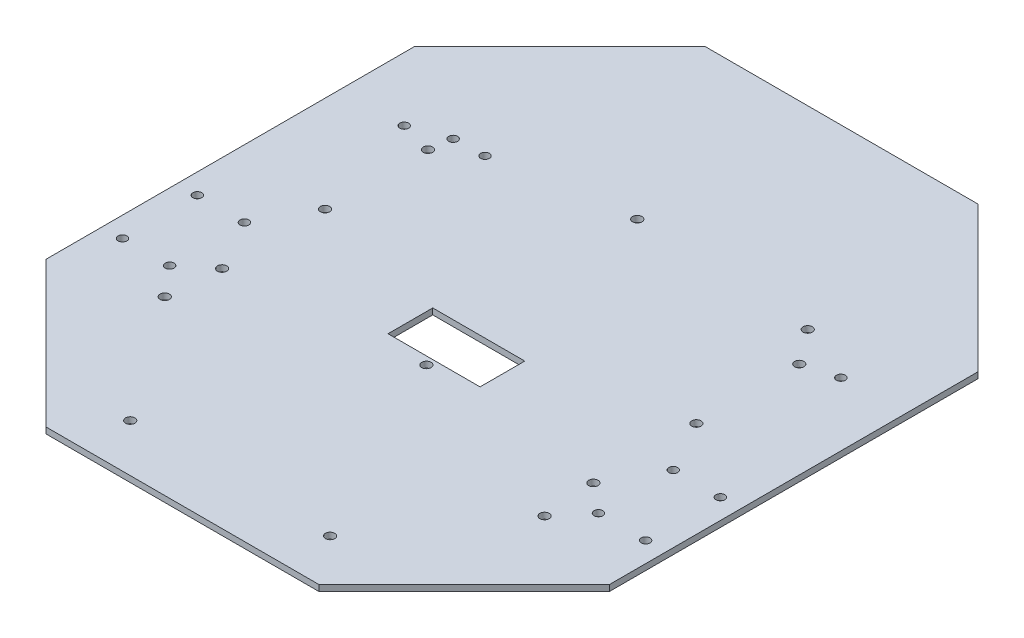
SolidWorks part; units mm, degrees
ref_plane "Front Plane" through (0, 0, 0) normal (0, 0, 1) x (1, 0, 0)
ref_plane "Top Plane" through (0, 0, 0) normal (0, 1, 0) x (1, 0, 0)
ref_plane "Right Plane" through (0, 0, 0) normal (1, 0, 0) x (0, 0, -1)
sketch "Sketch14" plane through (0, 0, 0) normal (0, 1, 0) x (1, 0, 0)
  line L1 (224, 92.7838) -> (92.7838, 224)
  line L2 (92.7838, 224) -> (-92.7838, 224)
  line L3 (-92.7838, 224) -> (-224, 92.7838)
  line L4 (-224, 92.7838) -> (-224, -92.7838)
  line L5 (-224, -92.7838) -> (-92.7838, -224)
  line L6 (-92.7838, -224) -> (92.7838, -224)
  line L7 (92.7838, -224) -> (224, -92.7838)
  line L8 (224, -92.7838) -> (224, 92.7838)
  circle A0 centre (0, 0) radius 224 construction
extrude "Boss-Extrude2" add sketch "Sketch14" along normal blind 4.12
sketch "Sketch16" plane through (0, 0, 0) normal (0, -1, 0) x (1, 0, 0)
  line L0 (-191.5, -224) -> (-191.5, 224)
  line L1 (-191.5, -224) -> (191.5, -224)
  line L2 (-191.5, 224) -> (191.5, 224)
  line L3 (191.5, -224) -> (191.5, 224)
  line L4 (-191.5, -224) -> (191.5, 224) construction
  line L5 (-191.5, 224) -> (191.5, -224) construction
  point P1 (0, 0)
  dimension "D1" = 383
ref_point "Point9"
ref_point "Point10"
sketch "Sketch17" plane through (0, 0, 0) normal (0, -1, 0) x (1, 0, 0)
  line L0 (191.5, 125.2838) -> (191.5, -125.742)
  line L1 (191.5, -125.742) -> (224, -92.7838)
  line L2 (224, -92.7838) -> (224, 92.7838)
  line L3 (224, 92.7838) -> (191.5, 125.2838)
extrude "Cut-Extrude2" cut sketch "Sketch17" against normal blind 4.12
ref_point "Point11"
ref_point "Point12"
sketch "Sketch18" plane through (0, 0, 0) normal (0, -1, 0) x (1, 0, 0)
  line L0 (-191.5, 125.2838) -> (-224, 92.7838)
  line L1 (-224, 92.7838) -> (-224, -92.7838)
  line L2 (-224, -92.7838) -> (-191.5, -125.2838)
  line L3 (-191.5, -125.2838) -> (-191.5, 125.2838)
extrude "Cut-Extrude3" cut sketch "Sketch18" against normal blind 4.12
hole_wizard "1/4 (0.25) Diameter Hole1" positions "Sketch19" profile "Sketch21" hole size "1/4" standard "ANSI Inch" end condition up to next
sketch "Sketch19" plane through (0, 4.12, 0) normal (0, 1, 0) x (1, 0, 0)
  point P2 (67.9635, -191.609)
  point P5 (-67.9265, -191.609)
  point P8 (-129.0643, -106.9889)
  point P11 (-126.1941, -70.8955)
  point P14 (-126.1941, -0.9185)
  point P17 (-126.1941, 69.0585)
  point P20 (-14.1039, 99.2591)
  point P23 (108.7305, 92.2995)
  point P26 (126.2311, 69.0585)
  point P29 (126.2311, -0.9185)
  point P32 (129.1013, -106.9889)
  point P35 (126.2311, -70.8955)
  point P38 (0.0185, -58.1955)
sketch "Sketch21" plane through (67.9635, 4.12, 191.609) normal (1, 0, 0) x (0, 0, 1)
  line L0 (0, 0) -> (0, 4.12)
  line L1 (0, 4.12) -> (3.175, 4.12)
  line L2 (3.175, 4.12) -> (3.175, 0)
  line L5 (3.175, 0) -> (0, 0)
  line L11 (0, -6.35) -> (0, 107.95) construction
  dimension "Thru Hole Dia." = 6.35
  dimension "Thru Hole Depth" = 4.12
sketch "Sketch22" plane through (0, 4.12, 0) normal (0, 1, 0) x (1, 0, 0)
  line L1 (31.1658, -52.8764) -> (-31.3997, -52.8764)
  line L2 (31.1658, -52.8764) -> (31.1658, -22.4822)
  line L3 (31.1658, -22.4822) -> (-31.3997, -22.4822)
  line L4 (-31.3997, -52.8764) -> (-31.3997, -22.4822)
extrude "Cut-Extrude4" cut sketch "Sketch22" against normal up to next
sketch "Sketch23" plane through (0, 0, 224) normal (0, 0, 1) x (1, 0, 0)
  line L0 (0, 4.12) -> (0, 0)
  line L1 (-92.7838, 4.12) -> (92.7838, 4.12) construction
  line L2 (-92.7838, 0) -> (92.7838, 0) construction
hole_wizard "Ø6.0mm Dowel Hole2" positions "Sketch24" profile "Sketch25" hole size "Ø6.0" standard "ANSI Metric" end condition up to next
sketch "Sketch24" plane through (0, 4.12, 0) normal (0, 1, 0) x (1, 0, 0)
  point P0 (-177.7815, -36.1589)
  point P3 (-177.7815, -86.9889)
  point P6 (-145.7415, -36.1589)
  point P9 (-145.7415, -86.9889)
  point P12 (145.7785, -86.9889)
  point P15 (177.8185, -86.9889)
  point P18 (177.8185, -36.1589)
  point P21 (145.7785, -36.1589)
  point P24 (0, 0)
  point P25 (0, 0)
  point P26 (0, 0)
  point P27 (0, 0)
  point P28 (0, 0)
  point P29 (0, 0)
  point P30 (0, 0)
  point P31 (0, 0)
sketch "Sketch25" plane through (-177.7815, 4.12, 36.1589) normal (1, 0, 0) x (0, 0, 1)
  line L0 (0, 0) -> (0, 4.12)
  line L1 (0, 4.12) -> (3, 4.12)
  line L2 (3, 4.12) -> (3, 0)
  line L5 (3, 0) -> (0, 0)
  line L11 (0, -6.35) -> (0, 107.95) construction
  dimension "Thru Hole Dia." = 6
  dimension "Thru Hole Depth" = 4.12
hole_wizard "Ø6.0mm Dowel Hole1" positions "Sketch26" profile "Sketch27" hole size "Ø6.0" standard "ANSI Metric" end condition up to next
sketch "Sketch26" plane through (0, 4.12, 0) normal (0, 1, 0) x (1, 0, 0)
  point P0 (-103.1515, 84.8073)
  point P3 (-124.0015, 84.0036)
  point P6 (0, 0)
  point P7 (0, 0)
sketch "Sketch27" plane through (-103.1515, 4.12, -84.8073) normal (1, 0, 0) x (0, 0, 1)
  line L0 (0, 0) -> (0, 4.12)
  line L1 (0, 4.12) -> (3, 4.12)
  line L2 (3, 4.12) -> (3, 0)
  line L5 (3, 0) -> (0, 0)
  line L11 (0, -6.35) -> (0, 107.95) construction
  dimension "Thru Hole Dia." = 6
  dimension "Thru Hole Depth" = 4.12
hole_wizard "Ø6.0mm Dowel Hole3" positions "Sketch28" profile "Sketch29" hole size "Ø6.0" standard "ANSI Metric" end condition up to next
sketch "Sketch28" plane through (0, 4.12, 0) normal (0, 1, 0) x (1, 0, 0)
  point P0 (-148.3962, 75.1271)
  point P2 (148.4173, 75.1508)
sketch "Sketch29" plane through (-148.3962, 4.12, -75.1271) normal (1, 0, 0) x (0, 0, 1)
  line L0 (0, 0) -> (0, 4.12)
  line L1 (0, 4.12) -> (3, 4.12)
  line L2 (3, 4.12) -> (3, 0)
  line L5 (3, 0) -> (0, 0)
  line L11 (0, -6.35) -> (0, 107.95) construction
  dimension "Thru Hole Dia." = 6
  dimension "Thru Hole Depth" = 4.12
